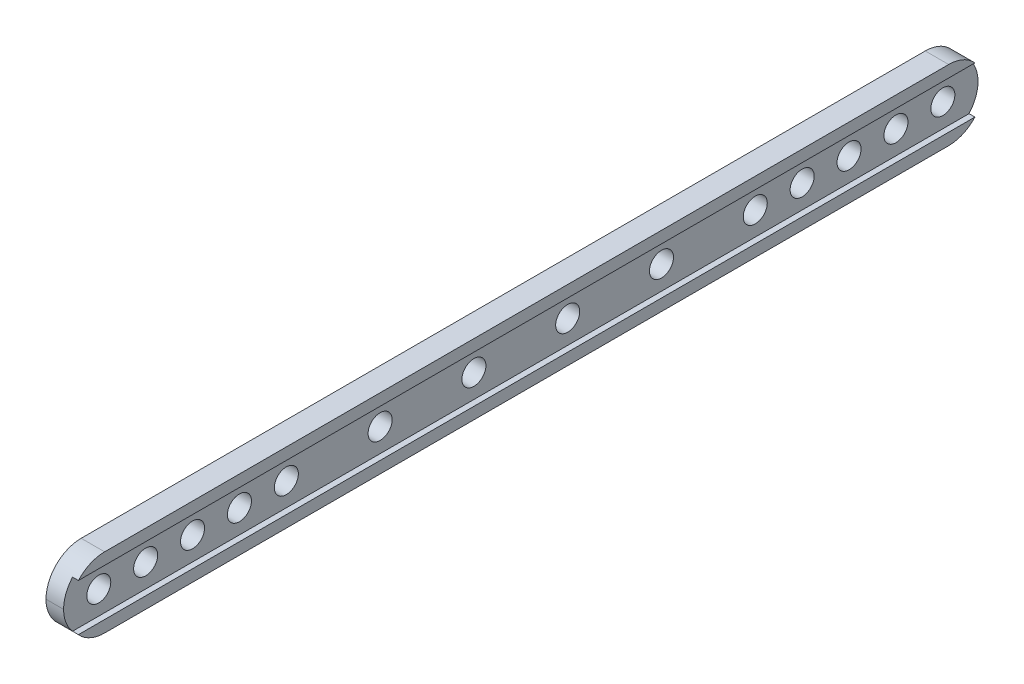
SolidWorks part; units mm, degrees
ref_plane "Front Plane" through (0, 0, 0) normal (0, 0, 1) x (1, 0, 0)
ref_plane "Top Plane" through (0, 0, 0) normal (0, 1, 0) x (1, 0, 0)
ref_plane "Right Plane" through (0, 0, 0) normal (1, 0, 0) x (0, 0, -1)
sketch "Sketch1" plane through (0, 0, 0) normal (0, 0, 1) x (1, 0, 0)
  line L0 (3, 6) -> (0, 6) construction
  line L1 (0, 0) -> (4, 0)
  line L2 (0, 0) -> (0, 12)
  line L3 (0, 12) -> (4, 12)
  line L4 (4, 0) -> (4, 2)
  line L5 (4, 10) -> (3, 10)
  line L7 (4, 2) -> (3, 2)
  line L8 (3, 10) -> (3, 2)
  line L9 (4, 10) -> (4, 12)
  dimension "D1" = 4
  dimension "D2" = 12
  dimension "D3" = 8
  dimension "D4" = 1
extrude "Boss-Extrude1" add sketch "Sketch1" against normal blind 156
ref_plane "Plane1" through (0, 0, -78) normal (0, 0, 1) x (1, 0, 0)
fillet "Fillet1" radius 6 4 edges at (2, 12, 0) (2, 0, 0) (2, 0, -156) (2, 12, -156)
sketch "Sketch2" plane through (0, 0, 0) normal (-1, 0, 0) x (0, 0, 1)
  circle A0 centre (-150, 6) radius 2.05
  dimension "D1" = 4.1
extrude "Cut-Extrude1" cut sketch "Sketch2" against normal through all
pattern_linear "LPattern1" count 9 spacing 8 along (0, 0, 1) skipping (5, 0), (7, 0) of "Cut-Extrude1"
mirror "Mirror1" about plane through (0, 0, -78) normal (0, 0, 1) of "LPattern1", "Cut-Extrude1"
